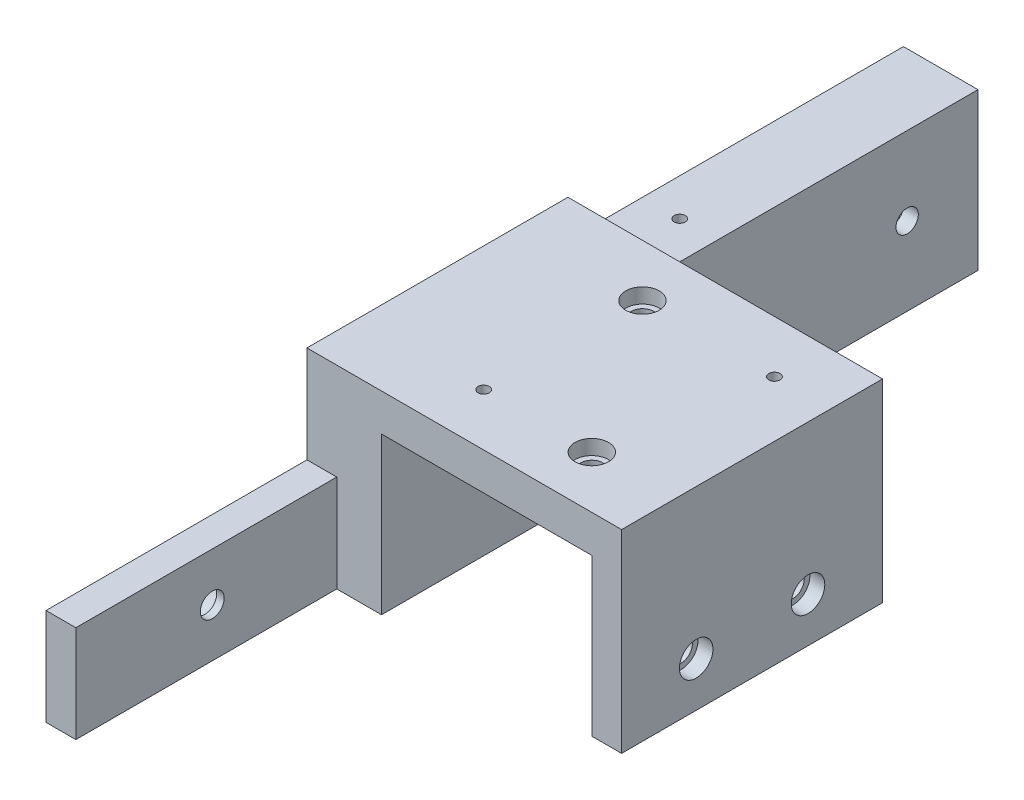
SolidWorks part; units mm, degrees
ref_plane "前视基准面" through (0, 0, 0) normal (0, 0, 1) x (1, 0, 0)
ref_plane "上视基准面" through (0, 0, 0) normal (0, 1, 0) x (1, 0, 0)
ref_plane "右视基准面" through (0, 0, 0) normal (1, 0, 0) x (0, 0, -1)
other "Configuration Table"
sketch "草图1" plane through (0, 0, 0) normal (0, 1, 0) x (1, 0, 0)
  line L5 (42.2, 0) -> (0, 0)
  line L6 (42.2, 0) -> (42.2, -35)
  line L19 (42.2, -35) -> (0, -35)
  line L20 (0, 0) -> (0, -35)
  line L21 (10, -35) -> (0, -35)
  line L22 (10, -35) -> (10, 45)
  line L23 (10, 45) -> (0, 45)
  line L24 (0, -35) -> (0, 45)
  line L29 (38.2, -35) -> (48.2, -35)
  line L30 (38.2, -35) -> (38.2, 0)
  line L31 (38.2, 0) -> (48.2, 0)
  line L32 (48.2, -35) -> (48.2, 0)
  point P0 (-90.6464, 22.0667)
  dimension "D1" = 35
  dimension "D2" = 38.2
  dimension "D3" = 10
  dimension "D4" = 80
  dimension "D5" = 4
extrude "凸台-拉伸1" add sketch "草图1" along normal blind 5 contours L5 L20 L19 L6
extrude "凸台-拉伸2" add sketch "草图1<14>" against normal blind 21 contours L30 L19 L6 L5 | L23 L24 L21 L22 region at (40.2, 0, 17.5)
sketch "草图1<14>" plane through (0, 0, 0) normal (0, 1, 0) x (1, 0, 0) same geometry as "草图1"
sketch "草图2" plane through (10, 0, 0) normal (1, 0, 0) x (0, 0, -1)
  line L0 (-35, 5) -> (-35, -21) construction
  line L1 (-35, -8) -> (-70, -8)
  line L2 (-35, -8) -> (-35, -21)
  line L3 (-35, -21) -> (-70, -21)
  line L4 (-70, -8) -> (-70, -21)
  line L5 (0, 0) -> (45, 0) construction
  line L6 (-35, -21) -> (45, -21) construction
  line L7 (-35, -14.5) -> (-70, -14.5) construction
  line L8 (0, 5) -> (0, -21) construction
  circle A1 centre (-67.5, -14.5) radius 0.5
  circle A4 centre (-29.4, -14.5) radius 3.1
  circle A5 centre (-51.7, -14.5) radius 3.1
  circle A6 centre (-8.399, -7.1) radius 3.1
  circle A7 centre (-51.7, -14.5) radius 1.6
  point P10 (-70, -14.5)
  dimension "D3" = 1
  dimension "D5" = 6.2
  dimension "D7" = 22.2666
  dimension "D9" = 3.2
  dimension "D1" = 35
  dimension "D2" = 14.5
  dimension "D4" = 15.8
  dimension "D6" = 22.3
  dimension "D8" = 8.399
extrude "凸台-拉伸3" add sketch "草图2" along normal blind 4 from surface contours L3 L4 L1 L2 starting at face at (0, -5.3333, -3.3333)
extrude "切除-拉伸1" cut sketch "草图2<3>" along normal blind 3 from surface contours A5 | A4 | A6 starting at face at (0, -6, 15)
sketch "草图2<3>" plane through (10, 0, 0) normal (1, 0, 0) x (0, 0, -1) same geometry as "草图2"
sketch "草图3" plane through (0, 5, 0) normal (0, 1, 0) x (1, 0, 0)
  line L0 (42.2, 0) -> (0, 0) construction
  line L1 (10, 0) -> (10, 45) construction
  line L2 (42.2, -35) -> (0, -35) construction
  line L3 (42.2, 0) -> (42.2, -35) construction
  circle A0 centre (17, -7) radius 2.25
  circle A1 centre (17, -7) radius 1.5
  circle A2 centre (31.2, -28) radius 2.25
  circle A3 centre (31.2, -28) radius 1.5
  dimension "D1" = 3
  dimension "D2" = 4.5
  dimension "D3" = 7
  dimension "D4" = 7
  dimension "D5" = 7
  dimension "D6" = 11
extrude "切除-拉伸2" cut sketch "草图3" against normal through all contours A3 | A1
extrude "切除-拉伸3" cut sketch "草图3<4>" against normal blind 2 contours A0 | A2
sketch "草图3<4>" plane through (0, 5, 0) normal (0, 1, 0) x (1, 0, 0) same geometry as "草图3"
sketch "草图4" plane through (0, -21, 0) normal (0, -1, 0) x (1, 0, 0)
  circle A0 centre (4.9985, -10.001) radius 0.75
  circle A1 centre (4.9985, -35.001) radius 0.75
  dimension "D1" = 1.5
extrude "切除-拉伸4" cut sketch "草图4" against normal blind 4 contours A1 | A0
extrude "切除-拉伸5" cut sketch "草图4<3>" along normal blind 4 from surface contours A0 starting at face at (5, 0, -22.5)
sketch "草图4<3>" plane through (0, -21, 0) normal (0, -1, 0) x (1, 0, 0) same geometry as "草图4"
sketch "草图5" plane through (0, 0, 0) normal (-1, 0, 0) x (0, 0, 1)
  line L0 (-45, -21) -> (-45, 0) construction
  circle A0 centre (-35.5, -10.5) radius 2.25
  circle A1 centre (-35.5, -10.5) radius 1.5
  point P5 (-45, -10.5)
  dimension "D1" = 3
  dimension "D2" = 4.5
  dimension "D3" = 9.5
extrude "切除-拉伸6" cut sketch "草图5" against normal through all contours A1
extrude "切除-拉伸7" cut sketch "草图5<3>" against normal offset from surface (8 mm away) 2 contours A0 up to face at (10, -10.5, -37)
sketch "草图5<3>" plane through (0, 0, 0) normal (-1, 0, 0) x (0, 0, 1) same geometry as "草图5"
sketch "草图6" plane through (42.2, 0, 0) normal (1, 0, 0) x (0, 0, -1)
  line L0 (0, -21) -> (-35, -21) construction
  line L1 (-35, 5) -> (-35, -21) construction
  line L2 (0, 5) -> (0, -21) construction
  circle A0 centre (-25, -15) radius 2.25
  circle A1 centre (-25, -15) radius 1.5
  circle A2 centre (-10, -15) radius 2.25
  circle A3 centre (-10, -15) radius 1.5
  dimension "D1" = 3
  dimension "D2" = 4.5
  dimension "D3" = 6
  dimension "D4" = 10
  dimension "D5" = 10
extrude "切除-拉伸8" cut sketch "草图6" against normal up to next contours A1 | A3
extrude "切除-拉伸9" cut sketch "草图6<3>" against normal blind 2 contours A0 | A2
sketch "草图6<3>" plane through (42.2, 0, 0) normal (1, 0, 0) x (0, 0, -1) same geometry as "草图6"
sketch "草图7" plane through (0, 5, 0) normal (0, 1, 0) x (1, 0, 0)
  circle A0 centre (16.6985, -27.999) radius 0.75
  circle A1 centre (34.6985, -6.999) radius 0.75
  dimension "D1" = 1.5
extrude "切除-拉伸10" cut sketch "草图7" against normal blind 4 contours A0 | A1
extrude "切除-拉伸11" cut sketch "草图2<4>" against normal through all contours A7
sketch "草图2<4>" plane through (10, 0, 0) normal (1, 0, 0) x (0, 0, -1) same geometry as "草图2"
